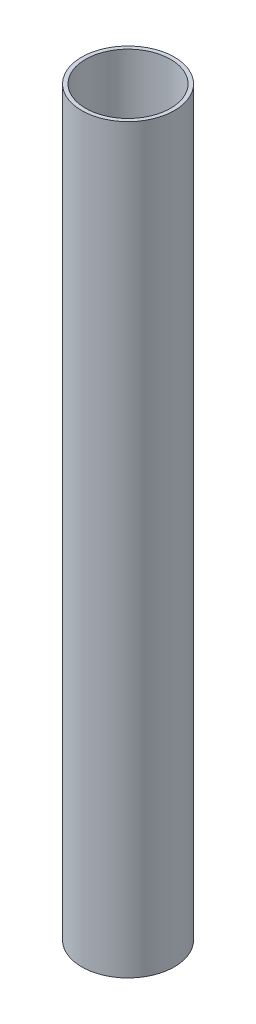
SolidWorks part; units mm, degrees
ref_plane "Front Plane" through (0, 0, 0) normal (0, 0, 1) x (1, 0, 0)
ref_plane "Top Plane" through (0, 0, 0) normal (0, 1, 0) x (1, 0, 0)
ref_plane "Right Plane" through (0, 0, 0) normal (1, 0, 0) x (0, 0, -1)
sketch "Sketch1" plane through (0, 0, 0) normal (0, 0, 1) x (1, 0, 0)
  line L0 (0, 0) -> (0, 304.8) construction
  line L1 (-19.05, 0) -> (-17.4625, 0)
  line L2 (-19.05, 0) -> (-19.05, 304.8)
  line L3 (-19.05, 304.8) -> (-17.4625, 304.8)
  line L4 (19.05, 0) -> (19.05, 304.8)
  line L5 (-17.4625, 0) -> (-17.4625, 304.8)
  line L6 (17.4625, 304.8) -> (17.4625, 0)
  line L7 (17.4625, 0) -> (19.05, 0)
  line L8 (17.4625, 304.8) -> (19.05, 304.8)
  dimension "D1" = 38.1
  dimension "12" = 304.8
  dimension "D2" = 1.5875
revolve "Revolve2" add sketch "Sketch1" angle 360 about L0 region at (-18.2563, 152.4, 0)
sketch "Sketch2" plane through (0, 0, 0) normal (0, 0, 1) x (1, 0, 0)
  line L1 (-17.4774, 183.5185) -> (17.1509, 183.5185)
  line L2 (-17.4774, 183.5185) -> (-17.4774, 188.9904)
  line L3 (-17.4774, 188.9904) -> (17.1509, 188.9904)
  line L4 (17.1509, 183.5185) -> (17.1509, 188.9904)
